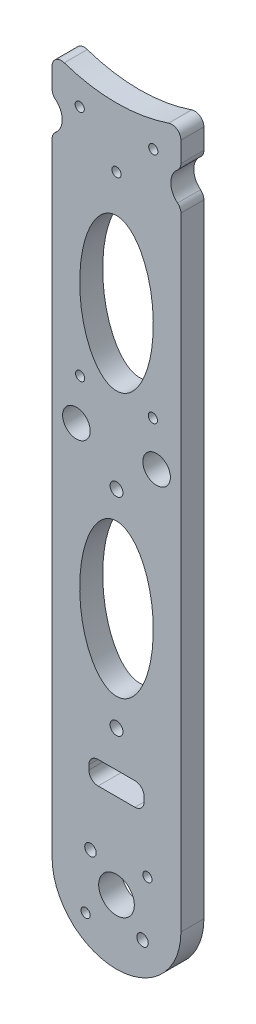
SolidWorks part; units mm, degrees
ref_plane "Front Plane" through (0, 0, 0) normal (0, 0, 1) x (1, 0, 0)
ref_plane "Top Plane" through (0, 0, 0) normal (0, 1, 0) x (1, 0, 0)
ref_plane "Right Plane" through (0, 0, 0) normal (1, 0, 0) x (0, 0, -1)
sketch "Sketch1" plane through (0, 0, 0) normal (0, 0, 1) x (1, 0, 0)
  line L0 (-14, 0) -> (-14, 135.3474)
  line L1 (0, 149.0732) -> (0, -14) construction
  line L2 (14, 0) -> (14, 135.3474)
  line L3 (-14, 0) -> (14, 0) construction
  line L4 (-5.6569, 5.6569) -> (5.6569, -5.6569) construction
  line L5 (0, 0) -> (-10.0045, -10.0045) construction
  line L6 (-10.0045, -10.0045) -> (8.2197, 8.2197) construction
  line L7 (-14, 144.6611) -> (-14, 149.0732)
  line L8 (-4, 18.5) -> (4, 18.5)
  line L9 (-6, 20.5) -> (-6, 21.5)
  line L10 (-4, 23.5) -> (4, 23.5)
  line L11 (6, 20.5) -> (6, 21.5)
  line L12 (-6, 18.5) -> (6, 23.5) construction
  line L13 (-6, 23.5) -> (6, 18.5) construction
  line L14 (14, 144.6611) -> (14, 149.0732)
  arc A0 (-14, 0) -> (14, 0) centre (0, 0) ccw
  arc A1 (-11.3514, 150.9651) -> (11.3514, 150.9651) centre (0, 184.0732) ccw
  circle A2 centre (-8, 144.3712) radius 1
  circle A3 centre (5.6569, -5.6569) radius 1.25
  circle A4 centre (-6.7175, -6.7175) radius 1
  circle A5 centre (6.7175, 6.7175) radius 1
  circle A6 centre (-5.6569, 5.6569) radius 1.25
  circle A7 centre (8, 144.3712) radius 1
  circle A8 centre (0, 136.0732) radius 1
  circle A9 centre (0, 136.0732) radius 1 construction
  circle A10 centre (-8, 144.3712) radius 1 construction
  circle A11 centre (8, 144.3712) radius 1 construction
  circle A12 centre (7.9033, 93.7383) radius 1
  circle A13 centre (0, 184.0732) radius 35 construction
  circle A14 centre (-5.6569, 5.6569) radius 1.25 construction
  circle A15 centre (-6.7175, -6.7175) radius 1.25 construction
  circle A16 centre (7.9033, 93.7383) radius 1 construction
  circle A17 centre (0, 31.3839) radius 1.4
  circle A18 centre (0, 76.3839) radius 1.4
  circle A19 centre (5.6569, -5.6569) radius 1.25 construction
  circle A20 centre (8.7156, 84.4537) radius 3
  circle A21 centre (8.7156, 84.4537) radius 1.45 construction
  arc A22 (6, 20.5) -> (4, 18.5) centre (4, 20.5) cw
  arc A23 (4, 23.5) -> (6, 21.5) centre (4, 21.5) cw
  arc A24 (-4, 23.5) -> (-6, 21.5) centre (-4, 21.5) ccw
  arc A25 (-6, 20.5) -> (-4, 18.5) centre (-4, 20.5) ccw
  arc A26 (-14, 149.0732) -> (-11.3514, 150.9651) centre (-12, 149.0732) cw
  arc A27 (11.3514, 150.9651) -> (14, 149.0732) centre (12, 149.0732) cw
  arc A28 (-13.2731, 143.1186) -> (-13.2731, 136.8899) centre (-15.8435, 140.0042) cw
  arc A29 (13.2731, 143.1186) -> (13.2731, 136.8899) centre (15.8435, 140.0042) ccw
  arc A30 (14, 135.3474) -> (13.2731, 136.8899) centre (12, 135.3474) ccw
  arc A31 (13.2731, 143.1186) -> (14, 144.6611) centre (12, 144.6611) ccw
  arc A32 (-14, 144.6611) -> (-13.2731, 143.1186) centre (-12, 144.6611) ccw
  arc A33 (-13.2731, 136.8899) -> (-14, 135.3474) centre (-12, 135.3474) ccw
  circle A34 centre (-7.9033, 93.7383) radius 1
  circle A35 centre (-8.7156, 84.4537) radius 3
  ellipse E0 centre (0, 53.8839) end of major axis (0, 70.3839) minor radius 8
  ellipse E1 centre (0, 111.3839) end of major axis (0, 127.8839) minor radius 8
  point P43 (0, 21)
  point P82 (-14, 151.9952)
  point P85 (14, 151.9952)
  point P94 (14, 136.4115)
  point P97 (14, 143.597)
  point P100 (-14, 143.597)
  point P103 (-14, 136.4115)
  dimension "D1" = 2.5
  dimension "D3" = 14
  dimension "D5" = 2
  dimension "D2" = 2
  dimension "D4" = 12
  dimension "D8" = 35
  dimension "D10" = 22.5
  dimension "D11" = 2
  dimension "D7" = 2.8
  dimension "D15" = 2
  dimension "D16" = 2
  dimension "D6" = 5
  dimension "D9" = 45
  dimension "D12" = 8
  dimension "D13" = 8
  dimension "D14" = 35
extrude "Boss-Extrude1" add sketch "Sketch1" along normal blind 5
sketch "Sketch2" plane through (0, 0, 5) normal (0, 0, 1) x (1, 0, 0)
  circle A0 centre (0, 0) radius 3.875
extrude "Cut-Extrude1" cut sketch "Sketch2" against normal up to next
